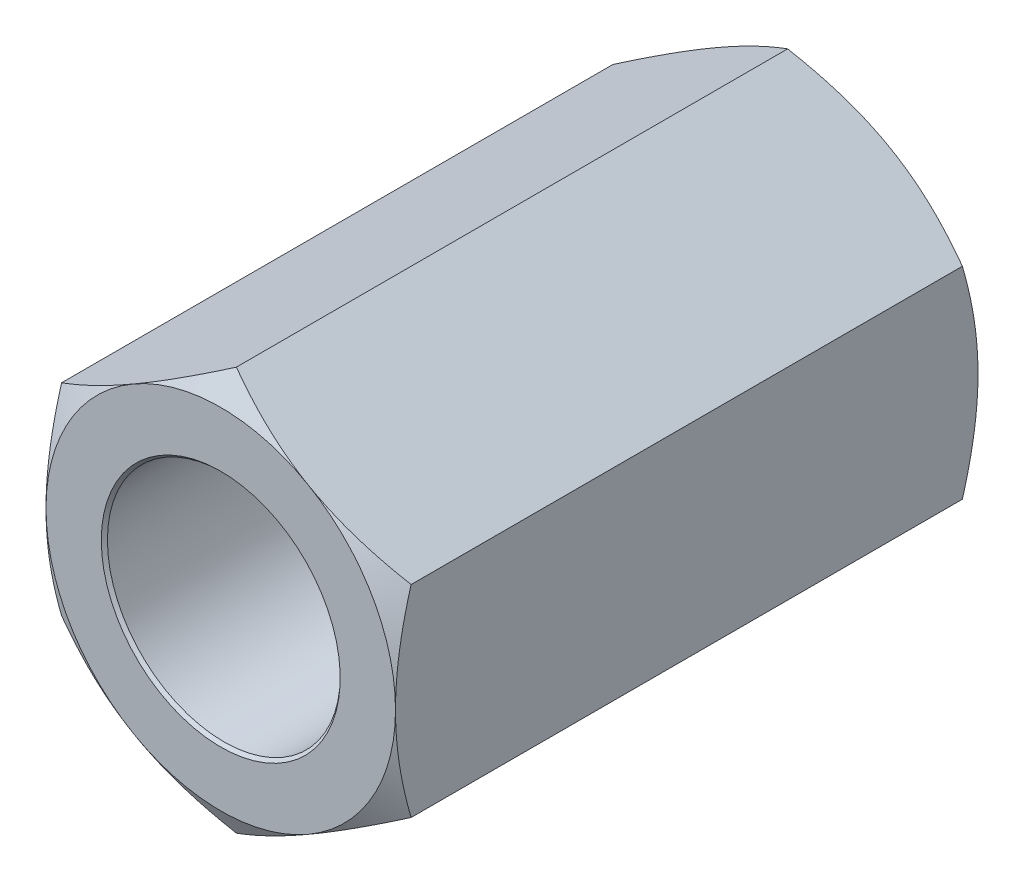
SolidWorks part; units mm, degrees
ref_plane "Front Plane" through (0, 0, 0) normal (0, 0, 1) x (1, 0, 0)
ref_plane "Top Plane" through (0, 0, 0) normal (0, 1, 0) x (1, 0, 0)
ref_plane "Right Plane" through (0, 0, 0) normal (1, 0, 0) x (0, 0, -1)
sketch "Sketch3" plane through (0, 0, 0) normal (1, 0, 0) x (0, 0, -1)
  line L0 (-5, 0) -> (5, 0) construction
  line L1 (0, 3) -> (0, -3) construction
  line L2 (-5, 2) -> (-5, -2) construction
  point P2 (0.2, 0)
  point P3 (-0.2, 0)
  dimension "Length" = 10
  dimension "Min Thread Length" = 4.8
  dimension "D1" = 4.8
  dimension "Thread Dia" = 4
  dimension "Hex" = 6
sketch "Sketch1" plane through (0, 0, 0) normal (0, 0, 1) x (1, 0, 0)
  line L1 (0, 3.4641) -> (-3, 1.7321)
  line L2 (-3, 1.7321) -> (-3, -1.7321)
  line L3 (-3, -1.7321) -> (0, -3.4641)
  line L4 (0, -3.4641) -> (3, -1.7321)
  line L5 (3, -1.7321) -> (3, 1.7321)
  line L6 (3, 1.7321) -> (0, 3.4641)
  circle A0 centre (0, 0) radius 3 construction
  circle A1 centre (0, 0) radius 2
extrude "Extrude1" add sketch "Sketch1" along normal up to vertex (5 mm away) and the other way up to vertex (5 mm away) up to point (0, 0, 5) other way up to point (0, 0, -5)
sketch "Sketch11" plane through (0, 0, -5) normal (0, 0, -1) x (-1, 0, 0)
  circle A0 centre (0, 0) radius 2 construction
  circle A1 centre (0, 0) radius 2
curve "Helix/Spiral1" pitch 0.7 height 10.7 turns 15.2857 parameters "Pitch"=0.7
sketch "Sketch12" plane through (0, 0, 0) normal (1, 0, 0) x (0, 0, -1)
  line L0 (5.4725, 2) -> (5, 2)
  line L1 (5.4725, 2) -> (5.28, 1.6666)
  line L2 (5.28, 1.6666) -> (5.1925, 1.6666)
  line L3 (5.1925, 1.6666) -> (5, 2)
  line L4 (5.2363, 1.6666) -> (5.2363, 2) construction
  line L5 (5.3762, 1.8333) -> (5.0963, 1.8333) construction
  dimension "D1" = 0.0875
  dimension "D2" = 0.28
  dimension "D3" = 60
sweep "Sweep1" [suppressed] add profiles "Sketch12" path "Helix/Spiral1"
sketch "Sketch6" plane through (0, 0, -5) normal (0, 0, -1) x (-1, 0, 0)
  line L6 (0, 3.4641) -> (-3, 1.7321)
  line L7 (-3, 1.7321) -> (-3, -1.7321)
  line L8 (-3, -1.7321) -> (0, -3.4641)
  line L9 (0, -3.4641) -> (3, -1.7321)
  line L10 (3, -1.7321) -> (3, 1.7321)
  line L11 (3, 1.7321) -> (0, 3.4641)
  line L12 (0, 3.4641) -> (-3, 1.7321)
  line L13 (-3, 1.7321) -> (-3, -1.7321)
  line L14 (-3, -1.7321) -> (0, -3.4641)
  line L15 (0, -3.4641) -> (3, -1.7321)
  line L16 (3, -1.7321) -> (3, 1.7321)
  line L17 (3, 1.7321) -> (0, 3.4641)
  dimension "D1" = 0
extrude "Extrude2" [suppressed] cut sketch "Sketch6" along normal through all
sketch "Sketch7" plane through (0, 0, -5) normal (0, 0, -1) x (-1, 0, 0)
  circle A2 centre (0, 0) radius 2.0508
  circle A3 centre (0, 0) radius 2.0508
  dimension "D1" = 0.0508
extrude "Extrude3" cut sketch "Sketch7" against normal through all draft 43
sketch "Sketch8" plane through (0, 0, -5) normal (0, 0, -1) x (-1, 0, 0)
  circle A0 centre (0, 0) radius 3 construction
  circle A1 centre (0, 0) radius 3
extrude "Extrude4" cut sketch "Sketch8" against normal through all draft 60 flip side to cut
mirror "Mirror1" about plane through (0, 0, 0) normal (0, 0, 1) of "Extrude4", "Extrude3"
sketch "Sketch9" [suppressed] plane through (0, 0, 0) normal (1, 0, 0) x (0, 0, -1)
  line L1 (-0.2, -1.8375) -> (0.2, -1.8375)
  line L2 (-0.2, -1.8375) -> (-0.2, 0)
  line L3 (-0.2, 0) -> (0.2, 0)
  line L4 (0.2, -1.8375) -> (0.2, 0)
  line L7 (-5, 0) -> (5, 0) construction
revolve "Revolve" [suppressed] add sketch "Sketch9" angle 360 about L0
sketch "Sketch10" [suppressed] plane through (0, 0, 0) normal (1, 0, 0) x (0, 0, -1)
  line L0 (5, 2) -> (0.2, 2)
  line L1 (-5, 2) -> (-0.2, 2)
  line L2 (0.2, 2) -> (0.2, -2)
  line L3 (-5, -2) -> (-0.2, -2)
  line L4 (-0.2, 2) -> (-0.2, -2)
  line L5 (0.2, -2) -> (5, -2)
equation "\"D1@Sketch3\" = \"Min Thread Length@Sketch3\""
equation "\"D3@Helix/Spiral1\" = \"Length@Sketch3\"+\"Pitch@Helix/Spiral1\""
equation "\"D1@Sketch12\" = \"Pitch@Helix/Spiral1\"*.125"
equation "\"D2@Sketch12\" = \"Pitch@Helix/Spiral1\"*.4"
